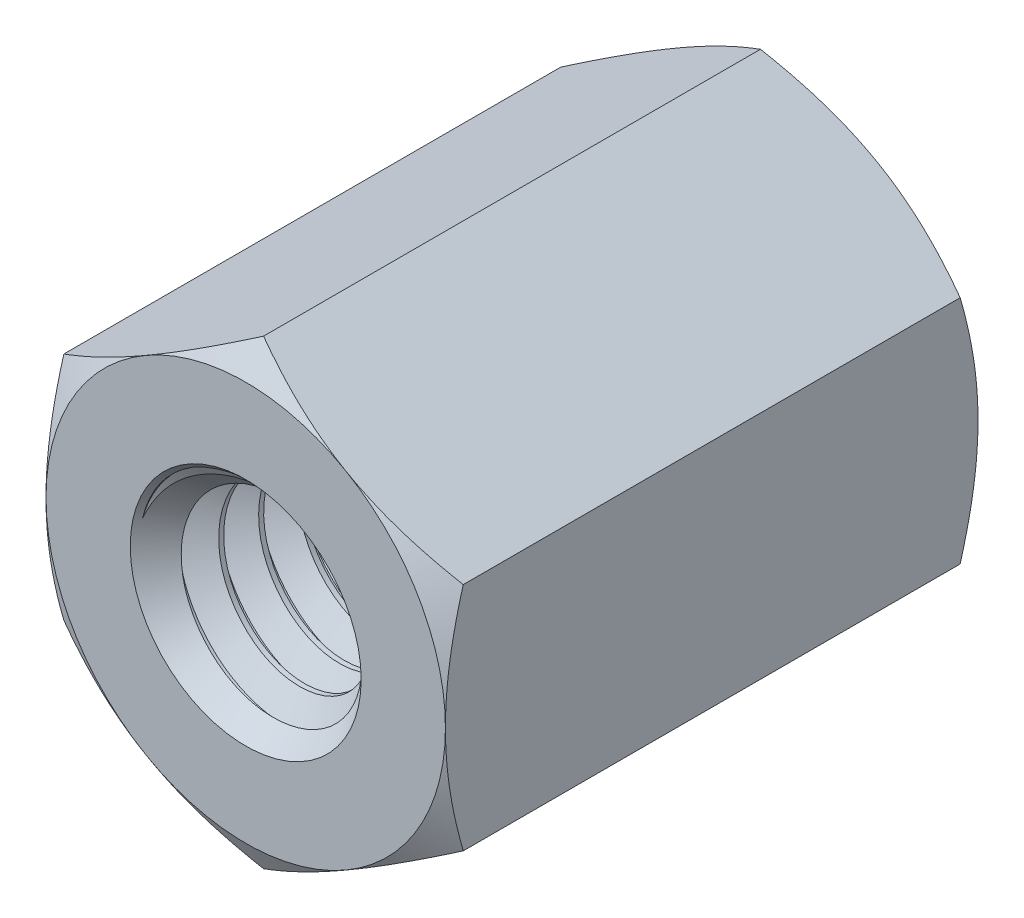
SolidWorks part; units mm, degrees
ref_plane "Front Plane" through (0, 0, 0) normal (0, 0, 1) x (1, 0, 0)
ref_plane "Top Plane" through (0, 0, 0) normal (0, 1, 0) x (1, 0, 0)
ref_plane "Right Plane" through (0, 0, 0) normal (1, 0, 0) x (0, 0, -1)
sketch "Sketch3" plane through (0, 0, 0) normal (1, 0, 0) x (0, 0, -1)
  line L0 (-3, 0) -> (3, 0) construction
  line L1 (0, 2.25) -> (0, -2.25) construction
  line L2 (-3, 1.25) -> (-3, -1.25) construction
  point P2 (-1.8, 0)
  point P3 (1.8, 0)
  dimension "D1" = 4.8
  dimension "Length" = 6
  dimension "Min Thread Length" = 4.8
  dimension "Thread Dia" = 2.5
  dimension "Hex" = 4.5
sketch "Sketch1" plane through (0, 0, 0) normal (0, 0, 1) x (1, 0, 0)
  line L1 (0, 2.5981) -> (-2.25, 1.299)
  line L2 (-2.25, 1.299) -> (-2.25, -1.299)
  line L3 (-2.25, -1.299) -> (0, -2.5981)
  line L4 (0, -2.5981) -> (2.25, -1.299)
  line L5 (2.25, -1.299) -> (2.25, 1.299)
  line L6 (2.25, 1.299) -> (0, 2.5981)
  circle A0 centre (0, 0) radius 2.25 construction
  circle A1 centre (0, 0) radius 1.25
extrude "Extrude1" add sketch "Sketch1" along normal up to vertex (3 mm away) and the other way up to vertex (3 mm away) up to point (0, 0, 3) other way up to point (0, 0, -3)
sketch "Sketch11" plane through (0, 0, -3) normal (0, 0, -1) x (-1, 0, 0)
  circle A0 centre (0, 0) radius 1.25 construction
  circle A1 centre (0, 0) radius 1.25
curve "Helix/Spiral1" pitch 0.45 height 6.45 radius 1.25 centre (0, 0, -3) axis (0, 0, 1) start towards (0, 1, 0) parameters "Pitch"=0.45
sketch "Sketch12" plane through (0, 0, 0) normal (1, 0, 0) x (0, 0, -1)
  line L0 (3.3938, 1.25) -> (3, 1.25)
  line L1 (3.3938, 1.25) -> (3.225, 0.9577)
  line L2 (3.225, 0.9577) -> (3.1688, 0.9577)
  line L3 (3.1688, 0.9577) -> (3, 1.25)
  line L4 (3.1969, 0.9577) -> (3.1969, 1.25) construction
  line L5 (3.3094, 1.1039) -> (3.0844, 1.1039) construction
  dimension "D1" = 0.0563
  dimension "D2" = 0.225
  dimension "D3" = 60
sweep "Sweep1" add profiles "Sketch12" path "Helix/Spiral1"
sketch "Sketch6" plane through (0, 0, -3) normal (0, 0, -1) x (-1, 0, 0)
  line L6 (0, 2.5981) -> (-2.25, 1.299)
  line L7 (-2.25, 1.299) -> (-2.25, -1.299)
  line L8 (-2.25, -1.299) -> (0, -2.5981)
  line L9 (0, -2.5981) -> (2.25, -1.299)
  line L10 (2.25, -1.299) -> (2.25, 1.299)
  line L11 (2.25, 1.299) -> (0, 2.5981)
  line L12 (0, 2.5981) -> (-2.25, 1.299)
  line L13 (-2.25, 1.299) -> (-2.25, -1.299)
  line L14 (-2.25, -1.299) -> (0, -2.5981)
  line L15 (0, -2.5981) -> (2.25, -1.299)
  line L16 (2.25, -1.299) -> (2.25, 1.299)
  line L17 (2.25, 1.299) -> (0, 2.5981)
  dimension "D1" = 0
extrude "Extrude2" cut sketch "Sketch6" along normal through all
sketch "Sketch7" plane through (0, 0, -3) normal (0, 0, -1) x (-1, 0, 0)
  circle A2 centre (0, 0) radius 1.3008
  circle A3 centre (0, 0) radius 1.3008
  dimension "D1" = 0.0508
extrude "Extrude3" cut sketch "Sketch7" against normal through all draft 43
sketch "Sketch8" plane through (0, 0, -3) normal (0, 0, -1) x (-1, 0, 0)
  circle A0 centre (0, 0) radius 2.25 construction
  circle A1 centre (0, 0) radius 2.25
extrude "Extrude4" cut sketch "Sketch8" against normal through all draft 60 flip side to cut
mirror "Mirror1" about plane through (0, 0, 0) normal (0, 0, 1) of "Extrude2", "Extrude3", "Extrude4"
sketch "Sketch9" [suppressed] plane through (0, 0, 0) normal (1, 0, 0) x (0, 0, -1)
  line L1 (-1.2, 1.1353) -> (1.2, 1.1353)
  line L2 (-1.2, 1.1353) -> (-1.2, 0)
  line L3 (-1.2, 0) -> (1.2, 0)
  line L4 (1.2, 1.1353) -> (1.2, 0)
  line L7 (-6, 0) -> (6, 0) construction
revolve "Revolve" [suppressed] add sketch "Sketch9" angle 360 about L0
sketch "Sketch10" [suppressed] plane through (0, 0, 0) normal (1, 0, 0) x (0, 0, -1)
  line L0 (6, 1.25) -> (1.2, 1.25)
  line L1 (-6, 1.25) -> (-1.2, 1.25)
  line L2 (1.2, 1.25) -> (1.2, -1.25)
  line L3 (-6, -1.25) -> (-1.2, -1.25)
  line L4 (-1.2, 1.25) -> (-1.2, -1.25)
  line L5 (1.2, -1.25) -> (6, -1.25)
equation "\"D1@Sketch3\" = \"Min Thread Length@Sketch3\""
equation "\"D3@Helix/Spiral1\" = \"Length@Sketch3\"+\"Pitch@Helix/Spiral1\""
equation "\"D1@Sketch12\" = \"Pitch@Helix/Spiral1\"*.125"
equation "\"D2@Sketch12\" = \"Pitch@Helix/Spiral1\"*.5"
